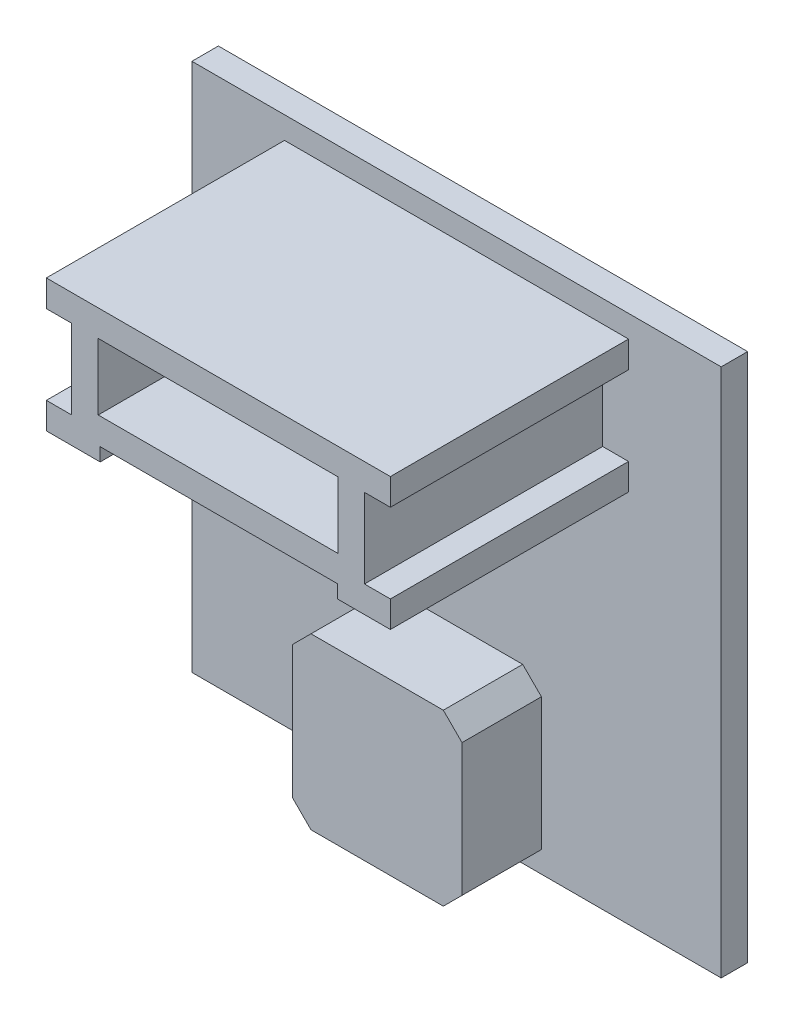
SolidWorks part; units mm, degrees
ref_plane "Plan de face" through (0, 0, 0) normal (0, 0, 1) x (1, 0, 0)
ref_plane "Plan de dessus" through (0, 0, 0) normal (0, 1, 0) x (1, 0, 0)
ref_plane "Plan de droite" through (0, 0, 0) normal (1, 0, 0) x (0, 0, -1)
sketch "Esquisse1" plane through (0, 0, 0) normal (0, 0, 1) x (1, 0, 0)
  line L1 (0, 0) -> (2, 0)
  line L2 (0, 0) -> (0, 2)
  line L3 (0, 2) -> (2, 2)
  line L4 (2, 0) -> (2, 2)
  dimension "D1" = 2
  dimension "D2" = 2
extrude "Boss.-Extru.1" add sketch "Esquisse1" along normal blind 0.1
sketch "Esquisse2" plane through (0, 0, 0.1) normal (0, 0, 1) x (1, 0, 0)
  line L0 (0.35, 1.916) -> (1.65, 1.916)
  line L1 (1.65, 1.916) -> (1.65, 1.8154)
  line L2 (1.65, 1.8154) -> (1.5521, 1.8154)
  line L3 (1.5521, 1.8154) -> (1.5521, 1.5154)
  line L4 (1.5521, 1.5154) -> (1.65, 1.5154)
  line L5 (1.65, 1.5154) -> (1.65, 1.4154)
  line L7 (0.35, 1.4154) -> (0.35, 1.5154)
  line L8 (0.35, 1.5154) -> (0.4459, 1.5154)
  line L9 (0.4459, 1.5154) -> (0.4459, 1.8154)
  line L10 (0.4459, 1.8154) -> (0.35, 1.8154)
  line L11 (0.35, 1.8154) -> (0.35, 1.916)
  line L12 (0.35, 1.4154) -> (0.5534, 1.4154)
  line L13 (0.5534, 1.4154) -> (0.5534, 1.4654)
  line L14 (0.5534, 1.4654) -> (1.45, 1.4654)
  line L15 (1.45, 1.4654) -> (1.45, 1.4154)
  line L16 (1.45, 1.4154) -> (1.65, 1.4154)
  line L17 (0.35, 1.916) -> (0, 1.916) construction
  line L18 (0, 2) -> (0, 0) construction
  line L19 (1.65, 1.916) -> (2, 1.916) construction
  line L20 (2, 0) -> (2, 2) construction
  line L21 (2, 2) -> (0, 2) construction
  dimension "D1" = 0.1006
  dimension "D2" = 0.1
  dimension "D3" = 0.1
  dimension "D4" = 0.3
  dimension "D5" = 1.3
  dimension "D6" = 1.3
  dimension "D7" = 0.2034
  dimension "D8" = 0.2
  dimension "D9" = 0.3
  dimension "D10" = 0.1006
  dimension "D11" = 0.084
  dimension "D12" = 0.05
  dimension "D13" = 0.35
  dimension "D14" = 0.0959
  dimension "D15" = 0.0979
extrude "Boss.-Extru.2" add sketch "Esquisse2" along normal blind 0.9
shell "Coque3" thickness 0.1 removed face at (1.0002, 1.6093, 1)
sketch "Esquisse3" plane through (0, 0, 0.1) normal (0, 0, 1) x (1, 0, 0)
  line L8 (0.6793, 0.5807) -> (0.6793, 0.0807)
  line L9 (0.6793, 0.0807) -> (0.75, 0.01)
  line L10 (0.75, 0.01) -> (1.25, 0.01)
  line L11 (1.25, 0.01) -> (1.3207, 0.0807)
  line L12 (1.3207, 0.0807) -> (1.3207, 0.5807)
  line L13 (1.3207, 0.5807) -> (1.25, 0.6514)
  line L14 (1.25, 0.6514) -> (0.75, 0.6514)
  line L15 (0.75, 0.6514) -> (0.6793, 0.5807)
  line L16 (0.75, 0.01) -> (0, 0.01) construction
  line L17 (0, 2) -> (0, 0) construction
  line L18 (1.25, 0.01) -> (2, 0.01) construction
  line L19 (2, 0) -> (2, 2) construction
  line L24 (0, 0) -> (2, 0) construction
  dimension "D1" = 135
  dimension "D2" = 135
  dimension "D3" = 135
  dimension "D4" = 0.5
  dimension "D5" = 0.5
  dimension "D6" = 0.1
  dimension "D7" = 0.01
extrude "Boss.-Extru.3" add sketch "Esquisse3" along normal blind 0.3
